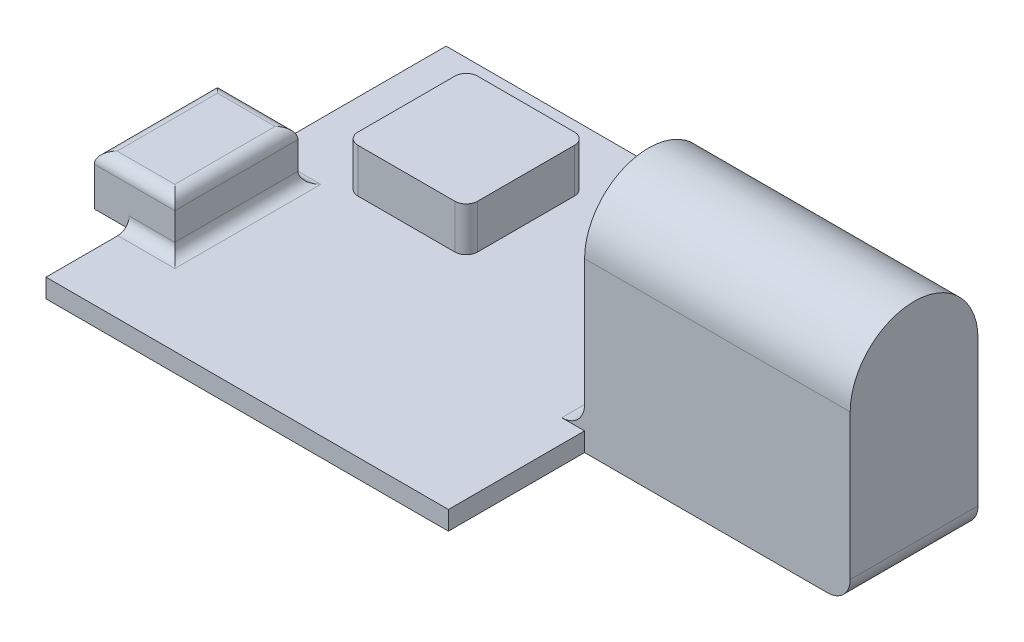
SolidWorks part; units mm, degrees
ref_plane "Front Plane" through (0, 0, 0) normal (0, 0, 1) x (1, 0, 0)
ref_plane "Top Plane" through (0, 0, 0) normal (0, 1, 0) x (1, 0, 0)
ref_plane "Right Plane" through (0, 0, 0) normal (1, 0, 0) x (0, 0, -1)
sketch "Sketch1" plane through (0, 0, 0) normal (0, 1, 0) x (1, 0, 0)
  line L1 (-17.65, 17.55) -> (17.65, 17.55)
  line L2 (-17.65, 17.55) -> (-17.65, -17.55)
  line L3 (-17.65, -17.55) -> (17.65, -17.55)
  line L4 (17.65, 17.55) -> (17.65, -17.55)
  line L5 (-17.65, 17.55) -> (17.65, -17.55) construction
  line L6 (-17.65, -17.55) -> (17.65, 17.55) construction
  line L7 (-11.13, 12.79) -> (-0.63, 12.79)
  line L8 (-11.13, 12.79) -> (-11.13, 2.29)
  line L9 (-11.13, 2.29) -> (-0.63, 2.29)
  line L10 (-0.63, 12.79) -> (-0.63, 2.29)
  line L11 (-11.13, 12.79) -> (-0.63, 2.29) construction
  line L12 (-11.13, 2.29) -> (-0.63, 12.79) construction
  line L13 (-13.65, 0.55) -> (-20.71, 0.55)
  line L14 (-13.65, 0.55) -> (-13.65, -10.25)
  line L15 (-13.65, -10.25) -> (-20.71, -10.25)
  line L16 (-20.71, 0.55) -> (-20.71, -10.25)
  point P0 (0, 0)
  point P6 (-6.7291, 6.6909)
  dimension "D1" = 35.1
  dimension "D2" = 35.3
  dimension "D3" = 10.5
  dimension "D4" = 10.8
  dimension "D5" = 7.3
  dimension "D6" = 4
  dimension "D7" = 3.06
  dimension "D8" = 4.76
  dimension "D9" = 6.52
extrude "Boss-Extrude1" add sketch "Sketch1" along normal blind 1.65 contours L14 L15 L2 L3 L4 L1 L13 L7 L10 L9 L8 | L15 L14 L13 L2 | L10 L7 L8 L9 region at (1.2199, 0, 0.5727) region at (-15.65, 0, 4.85) region at (-5.88, 0, -7.54)
extrude "Boss-Extrude2" add sketch "Sketch1<3>" along normal blind 4.4 from surface contours L15 L14 L13 L2 | L13 L16 L15 L2 region at (-15.65, 0, 4.85) region at (-19.18, 0, 4.85) starting at face at (0, 1.65, 0)
sketch "Sketch1<3>" plane through (0, 0, 0) normal (0, 1, 0) x (1, 0, 0) same geometry as "Sketch1"
extrude "Boss-Extrude3" add sketch "Sketch1<4>" along normal blind 3.86 from surface contours L10 L7 L8 L9 region at (-5.88, 0, -7.54) starting at face at (-7.825, 1.65, 2.425)
sketch "Sketch1<4>" plane through (0, 0, 0) normal (0, 1, 0) x (1, 0, 0) same geometry as "Sketch1"
fillet "Fillet1" radius 1 3 edges at (-13.65, 1.65, 4.85) (-15.65, 1.65, -0.55) (-15.65, 1.65, 10.25)
fillet "Fillet2" radius 1 4 edges at (-13.65, 6.05, 4.85) (-17.18, 6.05, 10.25) (-20.71, 6.05, 4.85) (-17.18, 6.05, -0.55)
sketch "Sketch2" plane through (-20.71, 0, 0) normal (-1, 0, 0) x (0, 0, 1)
  line L1 (1.0979, 2.9106) -> (8.8881, 2.9106)
  line L2 (1.0979, 2.9106) -> (1.0979, 4.2438)
  line L3 (1.0979, 4.2438) -> (8.8881, 4.2438)
  line L4 (8.8881, 2.9106) -> (8.8881, 4.2438)
extrude "Cut-Extrude1" cut sketch "Sketch2" against normal blind 2
fillet "Fillet3" radius 1 4 edges at (-11.13, 3.58, -12.79) (-0.63, 3.58, -12.79) (-0.63, 3.58, -2.29) (-11.13, 3.58, -2.29)
sketch "Sketch4" plane through (17.65, 0, 0) normal (1, 0, 0) x (0, 0, -1)
  line L0 (-5.605, 0) -> (-5.605, 14.7326)
  line L1 (17.55, 0) -> (-17.55, 0) construction
  line L2 (5.605, 14.7326) -> (5.605, 0)
  line L3 (5.605, 0) -> (-5.605, 0)
  arc A0 (-5.605, 14.7326) -> (5.605, 14.7326) centre (0, 14.7326) cw
  point P6 (0, 0)
  point P11 (29.8589, 17.0298)
  dimension "D1" = 20.3376
  dimension "D2" = 11.21
extrude "Boss-Extrude4" add sketch "Sketch4" along normal blind 23.3
fillet "Fillet4" radius 2 1 edges at (17.65, 1.65, 0)
fillet "Fillet5" radius 2 1 edges at (40.95, 0, 0)
